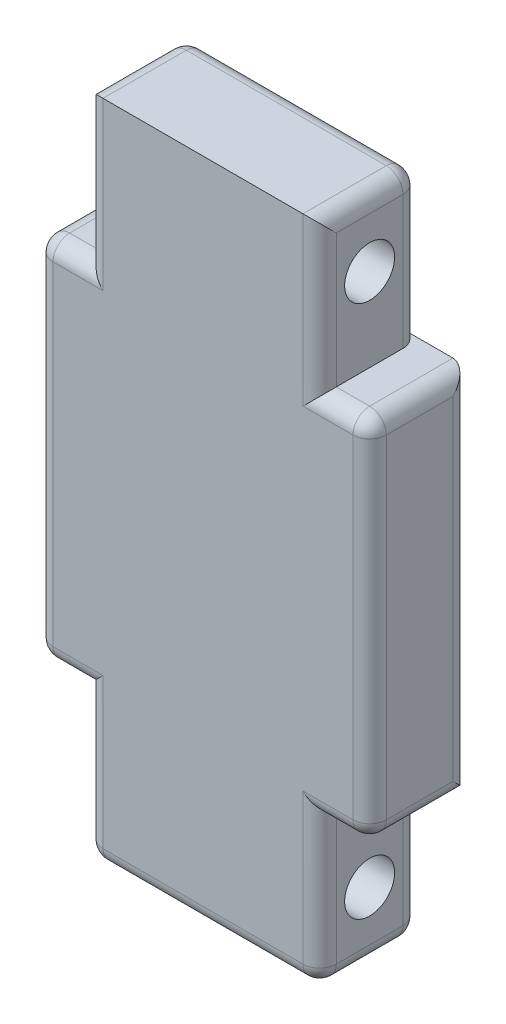
SolidWorks part; units mm, degrees
ref_plane "Front Plane" through (0, 0, 0) normal (0, 0, 1) x (1, 0, 0)
ref_plane "Top Plane" through (0, 0, 0) normal (0, 1, 0) x (1, 0, 0)
ref_plane "Right Plane" through (0, 0, 0) normal (1, 0, 0) x (0, 0, -1)
sketch "Sketch1" plane through (0, 0, 0) normal (0, 0, 1) x (1, 0, 0)
  line L0 (0, 0) -> (0, 400)
  line L1 (0, 400) -> (200, 400)
  line L2 (200, 400) -> (200, 0)
  line L3 (200, 0) -> (0, 0)
  dimension "D1" = 200
  dimension "D2" = 400
extrude "Boss-Extrude1" add sketch "Sketch1" along normal blind 60
sketch "Sketch2" plane through (200, 0, 0) normal (1, 0, 0) x (0, 0, -1)
  line L0 (-60, 400) -> (0, 400) construction
  line L1 (-60, 0) -> (0, 0) construction
  line L2 (-60, 0) -> (-60, 400) construction
  line L3 (0, 0) -> (0, 400) construction
  circle A0 centre (-30, 40) radius 15
  circle A1 centre (-30, 360) radius 15
  dimension "D1" = 40
  dimension "D2" = 30
  dimension "D3" = 40
  dimension "D4" = 30
  dimension "D5" = 30
  dimension "D6" = 30
extrude "Cut-Extrude1" cut sketch "Sketch2" against normal through all
sketch "Sketch3" plane through (0, 0, 0) normal (0, 0, -1) x (-1, 0, 0)
  line L0 (0, 90) -> (-30, 90)
  line L1 (0, 400) -> (0, 0) construction
  line L2 (-30, 90) -> (-30, 0)
  line L3 (0, 0) -> (-200, 0) construction
  line L4 (0, 25) -> (0, 55) construction
  line L5 (0, 90) -> (0, 0)
  line L6 (0, 0) -> (-30, 0)
  dimension "D1" = 90
  dimension "D2" = 30
extrude "Cut-Extrude2" cut sketch "Sketch3" against normal through all
ref_plane "Plane1" through (0, 200, 0) normal (0, 1, 0) x (1, 0, 0)
ref_plane "Plane2" through (100, 0, 0) normal (1, 0, 0) x (0, 0, -1)
mirror "Mirror1" about plane through (100, 0, 0) normal (1, 0, 0) of "Cut-Extrude2" second plane through (0, 200, 0) second plane normal (0, 1, 0)
fillet "Fillet1" radius 10 16 edges at (15, 310, 60) (15, 310, 0) (15, 90, 0) (15, 90, 60) (30, 0, 30) (100, 0, 0) (100, 400, 0) (30, 400, 30) (0, 310, 30) (0, 90, 30) (30, 355, 60) (30, 45, 60) (0, 200, 60) (30, 45, 0) (0, 200, 0) (30, 355, 0)
fillet "Fillet2" radius 10 16 edges at (170, 2.9289, 2.9289) (170, 397.0711, 2.9289) (32.9289, 2.9289, 57.0711) (200, 200, 0) (200, 200, 60) (170, 50, 0) (200, 90, 30) (170, 0, 35) (185, 90, 60) (170, 45, 60) (200, 310, 30) (170, 355, 60) (170, 400, 35) (185, 310, 60) (170, 350, 0) (105, 0, 60)
